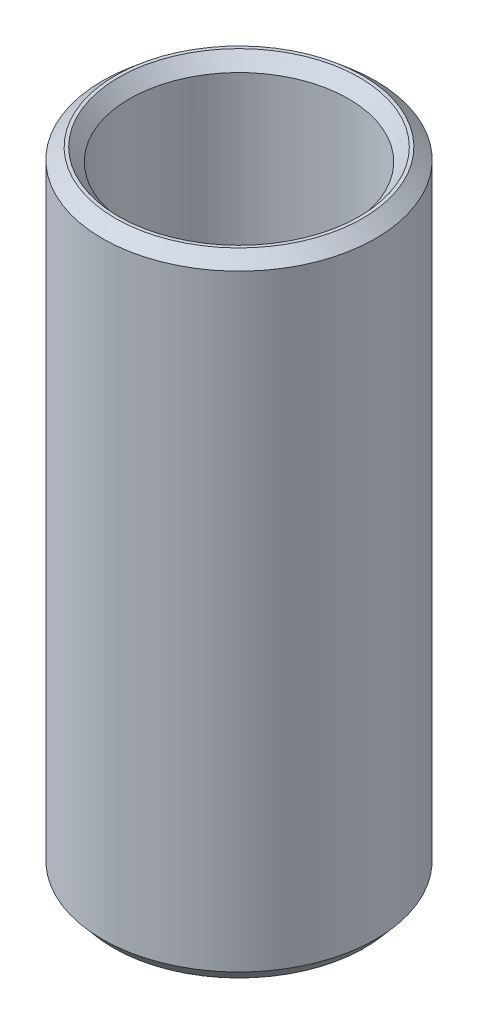
SolidWorks part; units mm, degrees
ref_plane "Front Plane" through (0, 0, 0) normal (0, 0, 1) x (1, 0, 0)
ref_plane "Top Plane" through (0, 0, 0) normal (0, 1, 0) x (1, 0, 0)
ref_plane "Right Plane" through (0, 0, 0) normal (1, 0, 0) x (0, 0, -1)
sketch "Sketch1" plane through (0, 0, 0) normal (0, 1, 0) x (1, 0, 0)
  circle A0 centre (0, 0) radius 30
  dimension "SLEEVE_OD" = 60
extrude "Boss-Extrude1" add sketch "Sketch1" along normal blind 138.5622
sketch "Sketch2" plane through (0, 0, 0) normal (0, 1, 0) x (1, 0, 0)
  circle A0 centre (0, 0) radius 24.0332
  dimension "BORE_D" = 48.0664
extrude "Cut-Extrude1" cut sketch "Sketch2" along normal through all
chamfer "Chamfer1" distance 2.4185 angle 49.539 4 edges at (0, 138.5622, 24.0332) (0, 0, 24.0332) (0, 0, 30) (0, 138.5622, 30) first distance on face at (0, 138.5622, 24.0332) first distance on face at (0, 0, 24.0332) first distance on face at (0, 138.5622, 30)
